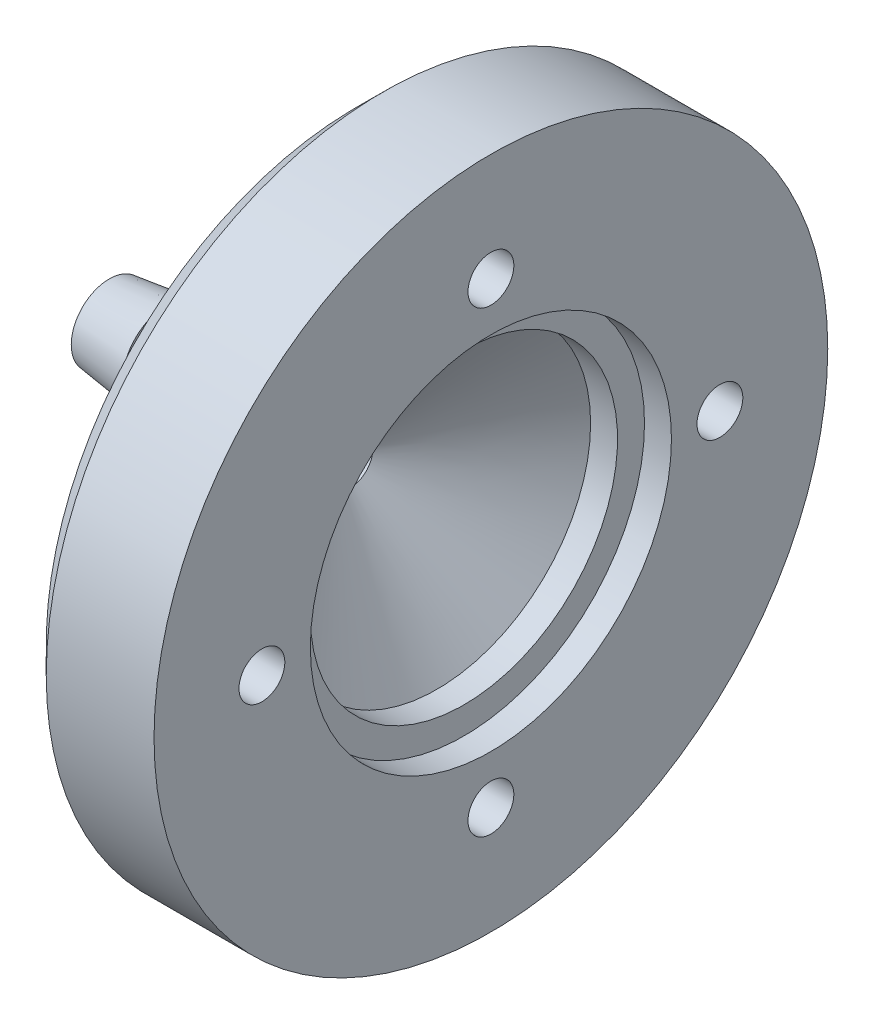
SolidWorks part; units mm, degrees
ref_plane "Front Plane" through (0, 0, 0) normal (0, 0, 1) x (1, 0, 0)
ref_plane "Top Plane" through (0, 0, 0) normal (0, 1, 0) x (1, 0, 0)
ref_plane "Right Plane" through (0, 0, 0) normal (1, 0, 0) x (0, 0, -1)
sketch "Sketch1" plane through (0, 0, 0) normal (0, 0, 1) x (1, 0, 0)
  line L0 (-801.9206, 0) -> (36107.5283, 0) construction
  line L3 (-13.5456, 3.375) -> (-13.5456, 2.82)
  line L8 (-17.879, 1.685) -> (0, 1.685)
  line L9 (-17.879, 1.685) -> (-17.879, 2.82)
  line L10 (10.4442, 13.4) -> (10.4442, 25)
  line L12 (10.4442, 25) -> (0.4442, 25)
  line L16 (10.4442, 13.4) -> (8.4442, 13.4)
  line L17 (8.4442, 13.4) -> (8.4442, 11.4)
  line L18 (0.4442, 25) -> (0.4442, 11.4)
  line L20 (0, 1.685) -> (6.4442, 11.4)
  line L21 (-17.879, 2.82) -> (-13.5456, 3.375)
  line L22 (6.4442, 11.4) -> (8.4442, 11.4)
  line L23 (-13.5456, 2.82) -> (-9.2123, 3.375)
  line L25 (-9.2123, 2.82) -> (-4.879, 3.375)
  line L26 (-9.2123, 3.375) -> (-9.2123, 2.82)
  line L27 (-4.879, 3.375) -> (0.4442, 11.4)
  dimension "D3" = 2
  dimension "D2" = 6.75
  dimension "D6" = 3.37
  dimension "D7" = 5.64
  dimension "D1" = 10
  dimension "D5" = 25
  dimension "D8" = 13.4
  dimension "D10" = 2
  dimension "D4" = 5
  dimension "D9" = 2
  dimension "D11" = 13
revolve "Revolve17" add sketch "Sketch1" angle 360 about L0
sketch "Sketch4" plane through (0.4442, 0, 0) normal (-1, 0, 0) x (0, 0, 1)
  circle A0 centre (0, 0) radius 16.9947 construction
  point P3 (0, 16.9947)
  point P7 (16.9947, 0)
  point P12 (-16.9947, 0)
  point P13 (0, -16.9947)
hole_wizard "M3 Clearance Hole1" positions "Sketch4" profile "Sketch5" hole size "M3" standard "ISO"
sketch "Sketch5" plane through (0.4442, -16.9947, 0) normal (0, 1, 0) x (0, 0, 1)
  line L0 (0, 0) -> (0, 11.0215)
  line L1 (0, 11.0215) -> (1.7, 10)
  line L2 (1.7, 10) -> (1.7, 0)
  line L5 (1.7, 0) -> (0, 0)
  line L10 (0, 11.0215) -> (-1.7, 10) construction
  line L11 (0, -6.35) -> (0, 107.95) construction
  dimension "Hole Dia." = 3.4
  dimension "Hole Depth" = 10
  dimension "Drill Angle" = 118
chamfer "Chamfer1" distance 2 angle 45 1 edges at (0.4442, 0, 25)
equation "\"D10@Sketch1\"=\"D3@Sketch1\""
equation "\"D9@Sketch1\"=\"D3@Sketch1\""
